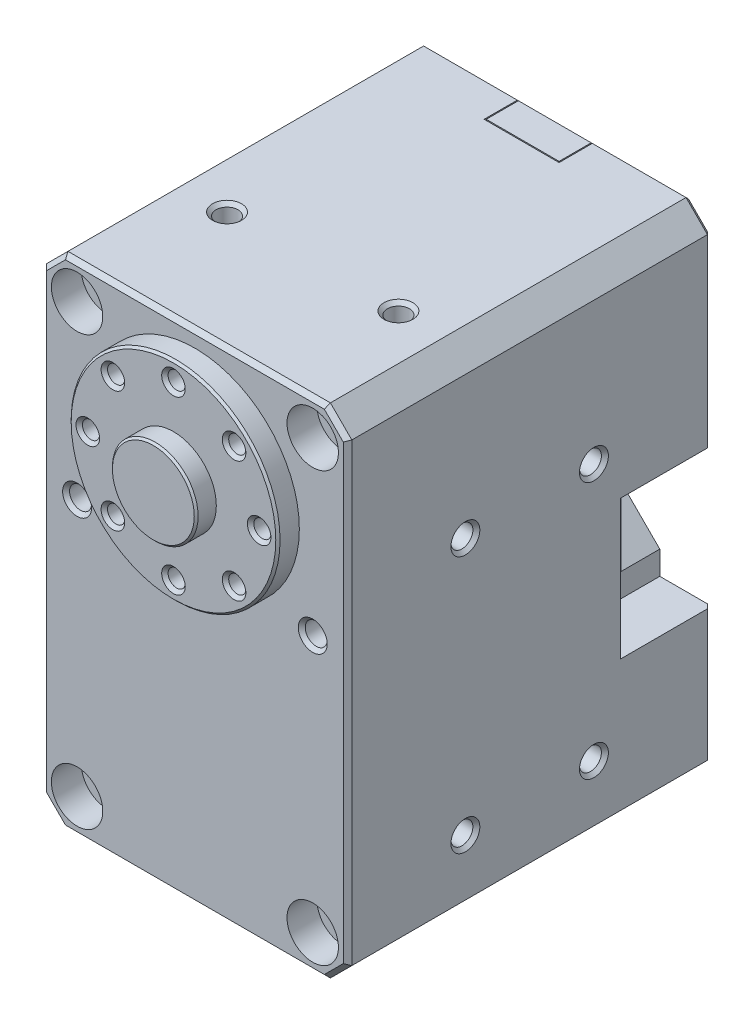
SolidWorks part; units mm, degrees
ref_plane "Front Plane" through (0, 0, 0) normal (0, 0, 1) x (1, 0, 0)
ref_plane "Top Plane" through (0, 0, 0) normal (0, 1, 0) x (1, 0, 0)
ref_plane "Right Plane" through (0, 0, 0) normal (1, 0, 0) x (0, 0, -1)
ref_plane "Plane1" through (0, 0, -17) normal (0, 0, -1) x (-1, 0, 0)
sketch "Sketch1" plane through (0, 0, -17) normal (0, 0, -1) x (-1, 0, 0)
  line L0 (5.5734, -8) -> (-5.5734, -8)
  arc A0 (-5.5734, -8) -> (5.5734, -8) centre (0, 0) ccw
extrude "Boss-Extrude1" add sketch "Sketch1" against normal blind 1
sketch "Sketch2" plane through (0, -8, 0) normal (0, 1, 0) x (-1, 0, 0)
  line L0 (14.25, -16) -> (14.25, -17)
  line L1 (14.25, -17) -> (-5.65, -17)
  line L2 (-5.65, -17) -> (-5.65, -16)
  line L3 (-5.65, -16) -> (14.25, -16)
extrude "Boss-Extrude2" add sketch "Sketch2" along normal blind 19.25
sketch "Sketch3" plane through (0, 0, -16) normal (0, 0, 1) x (1, 0, 0)
  line L0 (5.65, -8) -> (5.5734, -8)
  line L1 (-5.5734, -8) -> (-14.25, -8)
  line L2 (-14.25, -8) -> (-14.25, 11.25)
  line L3 (-14.25, 11.25) -> (5.65, 11.25)
  line L4 (5.65, 11.25) -> (5.65, -8)
  arc A0 (5.5734, -8) -> (-5.5734, -8) centre (0, 0) cw
extrude "Boss-Extrude3" add sketch "Sketch3" along normal blind 2.2
sketch "Sketch4" plane through (0, 0, -13.8) normal (0, 0, 1) x (1, 0, 0)
  line L0 (5.65, -35.25) -> (-14.25, -35.25)
  line L1 (-14.25, -35.25) -> (-14.25, 11.25)
  line L2 (-14.25, 11.25) -> (5.65, 11.25)
  line L3 (5.65, 11.25) -> (5.65, -35.25)
extrude "Boss-Extrude4" add sketch "Sketch4" along normal blind 30.8
sketch "Sketch5" plane through (0, 0, -17) normal (0, 0, -1) x (-1, 0, 0)
  line L0 (5.65, -8) -> (5.65, -7.9461)
  line L1 (5.5734, -8) -> (5.65, -8)
  arc A0 (5.65, -7.9461) -> (5.5734, -8) centre (0, 0) cw
extrude "Cut-Extrude1" cut sketch "Sketch5" against normal blind 1
ref_plane "Plane2" through (0, 0, -13.8) normal (0, 0, 1) x (1, 0, 0)
sketch "Sketch6" plane through (0, 0, -13.8) normal (0, 0, 1) x (1, 0, 0)
  line L0 (5.5734, -8) -> (-5.5734, -8)
  arc A0 (-5.5734, -8) -> (5.5734, -8) centre (0, 0) ccw
extrude "Cut-Extrude2" cut sketch "Sketch6" against normal blind 1.2
sketch "Sketch7" plane through (0, 0, -17) normal (0, 0, -1) x (-1, 0, 0)
  line L0 (-5.65, -8) -> (-5.5734, -8)
  line L1 (-5.65, -7.9461) -> (-5.65, -8)
  arc A0 (-5.5734, -8) -> (-5.65, -7.9461) centre (0, 0) cw
extrude "Cut-Extrude3" cut sketch "Sketch7" against normal blind 1
sketch "Sketch8" plane through (5.65, 0, 0) normal (1, 0, 0) x (0, 0, -1)
  line L0 (13.8, -35.25) -> (-17, -35.25)
  line L1 (-17, -35.25) -> (-17, 11.25)
  line L2 (-17, 11.25) -> (17, 11.25)
  line L3 (17, 11.25) -> (17, -8)
  line L4 (17, -8) -> (13.8, -8)
  line L5 (13.8, -8) -> (13.8, -35.25)
extrude "Boss-Extrude5" add sketch "Sketch8" along normal blind 8.6
sketch "Sketch9" plane through (0, 0, -13.8) normal (0, 0, -1) x (-1, 0, 0)
  line L0 (14.25, -15.5) -> (14.25, -35.25)
  line L1 (14.25, -35.25) -> (-14.25, -35.25)
  line L2 (-14.25, -35.25) -> (-14.25, -15.5)
  line L3 (-14.25, -15.5) -> (14.25, -15.5)
extrude "Boss-Extrude6" add sketch "Sketch9" along normal blind 3.2
sketch "Sketch10" plane through (0, 0, -17) normal (0, 0, -1) x (-1, 0, 0)
  line L0 (-3.5, 11.25) -> (-3.5, 9.45)
  line L1 (-3.5, 9.45) -> (3.5, 9.45)
  line L2 (3.5, 9.45) -> (3.5, 11.25)
  line L3 (3.5, 11.25) -> (-3.5, 11.25)
extrude "Cut-Extrude4" cut sketch "Sketch10" against normal blind 3.5
sketch "Sketch11" plane through (0, 0, -17) normal (0, 0, -1) x (-1, 0, 0)
  line L0 (-2.4, 9.45) -> (2.4, 9.45)
  arc A0 (2.4, 9.45) -> (-2.4, 9.45) centre (0, 0) ccw
extrude "Boss-Extrude7" add sketch "Sketch11" against normal blind 2
sketch "Sketch12" plane through (0, 0, -17) normal (0, 0, -1) x (-1, 0, 0)
  circle A0 centre (0, 0) radius 9.75
extrude "Boss-Extrude8" add sketch "Sketch12" along normal blind 2
ref_plane "Plane3" through (0, 0, -15) normal (0, 0, 1) x (1, 0, 0)
sketch "Sketch13" plane through (0, 0, -15) normal (0, 0, 1) x (1, 0, 0)
  line L0 (1.9647, 9.55) -> (3.4, 9.55)
  line L1 (3.4, 9.55) -> (3.4, 11.25)
  line L2 (3.4, 11.25) -> (-3.4, 11.25)
  line L3 (-3.4, 11.25) -> (-3.4, 9.55)
  line L4 (-3.4, 9.55) -> (-1.9647, 9.55)
  arc A0 (-1.9647, 9.55) -> (1.9647, 9.55) centre (0, 0) cw
extrude "Boss-Extrude9" add sketch "Sketch13" against normal blind 2
sketch "Sketch14" plane through (0, 0, -17) normal (0, 0, -1) x (-1, 0, 0)
  line L0 (9.4, -21) -> (14.25, -21)
  line L1 (14.25, -21) -> (14.25, -15.5)
  line L2 (14.25, -15.5) -> (9.4, -15.5)
  line L3 (9.4, -15.5) -> (9.4, -21)
extrude "Cut-Extrude5" cut sketch "Sketch14" against normal blind 3.2
ref_plane "Plane4" through (0, 0, -13.8) normal (0, 0, -1) x (-1, 0, 0)
ref_plane "Plane5" through (0, 0, -8.5) normal (0, 0, 1) x (1, 0, 0)
sketch "Sketch16" plane through (0, 0, -8.5) normal (0, 0, 1) x (1, 0, 0)
  line L0 (-14.25, -21) -> (-9.4, -21)
  line L1 (-9.4, -21) -> (-9.4, -8)
  line L2 (-9.4, -8) -> (-14.25, -8)
  line L3 (-14.25, -8) -> (-14.25, -21)
extrude "Cut-Extrude6" cut sketch "Sketch16" against normal up to surface up to plane "Plane4"
sketch "Sketch17" plane through (0, 0, -17) normal (0, 0, -1) x (-1, 0, 0)
  line L0 (-9.4, -21) -> (-9.4, -15.5)
  line L1 (-9.4, -15.5) -> (-14.25, -15.5)
  line L2 (-14.25, -15.5) -> (-14.25, -21)
  line L3 (-14.25, -21) -> (-9.4, -21)
extrude "Cut-Extrude7" cut sketch "Sketch17" against normal blind 3.2
sketch "Sketch19" plane through (0, 0, -8.5) normal (0, 0, 1) x (1, 0, 0)
  line L0 (14.25, -8) -> (9.4, -8)
  line L1 (9.4, -8) -> (9.4, -21)
  line L2 (9.4, -21) -> (14.25, -21)
  line L3 (14.25, -21) -> (14.25, -8)
extrude "Cut-Extrude8" cut sketch "Sketch19" against normal up to surface up to plane "Plane4"
ref_plane "Plane6" through (0, 8, 0) normal (0, 1, 0) x (1, 0, 0)
sketch "Sketch20" plane through (0, 8, 0) normal (0, 1, 0) x (1, 0, 0)
  line L0 (-9.65, 8) -> (-11, 8)
  line L1 (-11, 8) -> (-11, 0.8841)
  line L2 (-11, 0.8841) -> (-9.975, 1.5)
  line L3 (-9.975, 1.5) -> (-9.975, 7.675)
  line L4 (-9.975, 7.675) -> (-9.65, 8)
  line L5 (-11, 8) -> (-11, 0.884) construction
revolve "Cut-Revolve1" cut sketch "Sketch20" angle 360 about L5 reverse direction yes
ref_plane "Plane7" through (0, -32, 0) normal (0, 1, 0) x (1, 0, 0)
sketch "Sketch21" plane through (0, -32, 0) normal (0, 1, 0) x (1, 0, 0)
  line L0 (12.35, 8) -> (11, 8)
  line L1 (11, 8) -> (11, 0.8841)
  line L2 (11, 0.8841) -> (12.025, 1.5)
  line L3 (12.025, 1.5) -> (12.025, 7.675)
  line L4 (12.025, 7.675) -> (12.35, 8)
  line L5 (11, 8) -> (11, 0.884) construction
revolve "Cut-Revolve2" cut sketch "Sketch21" angle 360 about L5 reverse direction yes
sketch "Sketch22" plane through (0, -32, 0) normal (0, 1, 0) x (1, 0, 0)
  line L0 (-9.65, 8) -> (-11, 8)
  line L1 (-11, 8) -> (-11, 0.8841)
  line L2 (-11, 0.8841) -> (-9.975, 1.5)
  line L3 (-9.975, 1.5) -> (-9.975, 7.675)
  line L4 (-9.975, 7.675) -> (-9.65, 8)
  line L5 (-11, 8) -> (-11, 0.884) construction
revolve "Cut-Revolve3" cut sketch "Sketch22" angle 360 about L5 reverse direction yes
chamfer "Chamfer1" distance 2 angle 45 4 edges at (-14.25, -35.25, 0) (14.25, -35.25, 0) (-14.25, 11.25, 0) (14.25, 11.25, 0)
chamfer "Chamfer2" distance 3.3 angle 45 2 edges at (-9.4, -15.5, -15.4) (9.4, -15.5, -15.4)
chamfer "Chamfer3" distance 0.4 angle 45 22 edges at (13.25, -34.25, 17) (14.25, -12, 17) (0, -35.25, 17) (13.25, 10.25, 17) (-13.25, -34.25, 17) (0, 11.25, 17) (-14.25, -12, 17) (-13.25, 10.25, 17) (14.25, -27.125, -17) (13.25, -34.25, -17) (0, -35.25, -17) (-14.25, -27.125, -17) (-13.25, -34.25, -17) (-7.875, 11.25, -17) (-14.25, 0.625, -17) (-13.25, 10.25, -17) (0, 11.25, -17) (-9.4, -13.4, -13.8) (7.875, 11.25, -17) (14.25, 0.625, -17) (13.25, 10.25, -17) (9.4, -13.4, -13.8)
chamfer "Chamfer4" distance 0.2 angle 45 1 edges at (-9.75, 0, -19)
sketch "Sketch29" plane through (0, 0, -15) normal (0, 0, 1) x (1, 0, 0)
  line L0 (-3.4, 9.55) -> (-3.4, 11.25)
  line L1 (-3.4, 11.25) -> (3.4, 11.25)
  line L2 (3.4, 11.25) -> (3.4, 9.55)
  line L3 (3.4, 9.55) -> (-3.4, 9.55)
extrude "Boss-Extrude10" add sketch "Sketch29" along normal blind 1.4
hole_wizard "CBORE for M4 Hex Head Machine Screw1" positions "Sketch31" profile "Sketch30" counterbore size "M4" standard "ANSI Metric"
sketch "Sketch31" plane through (0, 0, -8) normal (0, 0, 1) x (1, 0, 0)
  point P0 (-11, -32)
sketch "Sketch30" plane through (-11, -32, -8) normal (1, 0, 0) x (0, -1, 0)
  line L0 (0, 0) -> (0, 9)
  line L1 (0, 9) -> (2.4, 9)
  line L2 (2.4, 9) -> (2.4, 6.2)
  line L3 (2.4, 6.2) -> (1.3, 6.2)
  line L4 (1.3, 6.2) -> (1.3, 0)
  line L5 (1.3, 0) -> (0, 0)
  line L10 (0, 9) -> (-2.4, 9) construction
  line L11 (0, -6.35) -> (0, 107.95) construction
  dimension "Hole Dia." = 4.8
  dimension "Hole Depth" = 9
  dimension "C'Bore Dia." = 2.6
  dimension "C'Bore Depth" = 6.2
  dimension "Drill Angle" = 180
hole_wizard "CBORE for M4 Hex Head Machine Screw2" positions "Sketch33" profile "Sketch32" counterbore size "M4" standard "ANSI Metric"
sketch "Sketch33" plane through (0, 0, -8) normal (0, 0, 1) x (1, 0, 0)
  point P0 (11, -32)
sketch "Sketch32" plane through (11, -32, -8) normal (1, 0, 0) x (0, -1, 0)
  line L0 (0, 0) -> (0, 9)
  line L1 (0, 9) -> (2.4, 9)
  line L2 (2.4, 9) -> (2.4, 6.2)
  line L3 (2.4, 6.2) -> (1.3, 6.2)
  line L4 (1.3, 6.2) -> (1.3, 0)
  line L5 (1.3, 0) -> (0, 0)
  line L10 (0, 9) -> (-2.4, 9) construction
  line L11 (0, -6.35) -> (0, 107.95) construction
  dimension "Hole Dia." = 4.8
  dimension "Hole Depth" = 9
  dimension "C'Bore Dia." = 2.6
  dimension "C'Bore Depth" = 6.2
  dimension "Drill Angle" = 180
hole_wizard "CBORE for M4 Hex Head Machine Screw3" positions "Sketch35" profile "Sketch34" counterbore size "M4" standard "ANSI Metric"
sketch "Sketch35" plane through (0, 0, -8) normal (0, 0, 1) x (1, 0, 0)
  point P0 (-11, 8)
sketch "Sketch34" plane through (-11, 8, -8) normal (1, 0, 0) x (0, -1, 0)
  line L0 (0, 0) -> (0, 9)
  line L1 (0, 9) -> (2.4, 9)
  line L2 (2.4, 9) -> (2.4, 6.2)
  line L3 (2.4, 6.2) -> (1.3, 6.2)
  line L4 (1.3, 6.2) -> (1.3, 0)
  line L5 (1.3, 0) -> (0, 0)
  line L10 (0, 9) -> (-2.4, 9) construction
  line L11 (0, -6.35) -> (0, 107.95) construction
  dimension "Hole Dia." = 4.8
  dimension "Hole Depth" = 9
  dimension "C'Bore Dia." = 2.6
  dimension "C'Bore Depth" = 6.2
  dimension "Drill Angle" = 180
sketch "Sketch45" plane through (0, 8, 0) normal (0, 1, 0) x (1, 0, 0)
  line L0 (13.4, 17) -> (11, 17)
  line L1 (11, 17) -> (11, 0.8841)
  line L2 (11, 0.8841) -> (12.025, 1.5)
  line L3 (12.025, 1.5) -> (12.025, 7.675)
  line L4 (12.025, 7.675) -> (12.35, 8)
  line L5 (12.35, 8) -> (12.3, 8)
  line L6 (12.3, 8) -> (12.3, 14.2)
  line L7 (12.3, 14.2) -> (13.4, 14.2)
  line L8 (13.4, 14.2) -> (13.4, 17)
  line L9 (11, 17) -> (11, 0.884) construction
revolve "Cut-Revolve4" cut sketch "Sketch45" angle 360 about L1 reverse direction yes
ref_plane "Plane8" through (0, 8, 0) normal (0, -1, 0) x (-1, 0, 0)
sketch "Sketch56" plane through (0, 8, 0) normal (0, -1, 0) x (-1, 0, 0)
  line L0 (8.6, -17) -> (11, -17)
  line L1 (11, -17) -> (11, -0.8841)
  line L2 (11, -0.8841) -> (9.975, -1.5)
  line L3 (9.975, -1.5) -> (9.975, -9.675)
  line L4 (9.975, -9.675) -> (9.65, -10)
  line L5 (9.65, -10) -> (9.7, -10)
  line L6 (9.7, -10) -> (9.7, -14.2)
  line L7 (9.7, -14.2) -> (8.6, -14.2)
  line L8 (8.6, -14.2) -> (8.6, -17)
  line L9 (11, -17) -> (11, -0.884) construction
revolve "Cut-Revolve5" cut sketch "Sketch56" angle 360 about L9 reverse direction yes
ref_plane "Plane9" through (0, -32, 0) normal (0, -1, 0) x (-1, 0, 0)
sketch "Sketch68" plane through (0, -32, 0) normal (0, -1, 0) x (-1, 0, 0)
  line L0 (-13.4, -17) -> (-11, -17)
  line L1 (-11, -17) -> (-11, -0.8841)
  line L2 (-11, -0.8841) -> (-12.025, -1.5)
  line L3 (-12.025, -1.5) -> (-12.025, -9.675)
  line L4 (-12.025, -9.675) -> (-12.35, -10)
  line L5 (-12.35, -10) -> (-12.3, -10)
  line L6 (-12.3, -10) -> (-12.3, -14.2)
  line L7 (-12.3, -14.2) -> (-13.4, -14.2)
  line L8 (-13.4, -14.2) -> (-13.4, -17)
  line L9 (-11, -17) -> (-11, -0.884) construction
revolve "Cut-Revolve6" cut sketch "Sketch68" angle 360 about L9 reverse direction yes
sketch "Sketch81" plane through (0, -32, 0) normal (0, -1, 0) x (-1, 0, 0)
  line L0 (8.6, -17) -> (11, -17)
  line L1 (11, -17) -> (11, -0.8841)
  line L2 (11, -0.8841) -> (9.975, -1.5)
  line L3 (9.975, -1.5) -> (9.975, -9.675)
  line L4 (9.975, -9.675) -> (9.65, -10)
  line L5 (9.65, -10) -> (9.7, -10)
  line L6 (9.7, -10) -> (9.7, -14.2)
  line L7 (9.7, -14.2) -> (8.6, -14.2)
  line L8 (8.6, -14.2) -> (8.6, -17)
  line L9 (11, -17) -> (11, -0.884) construction
revolve "Cut-Revolve7" cut sketch "Sketch81" angle 360 about L9 reverse direction yes
sketch "Sketch93" plane through (0, 8, 0) normal (0, -1, 0) x (-1, 0, 0)
  line L0 (-13.4, -17) -> (-11, -17)
  line L1 (-11, -17) -> (-11, -0.8841)
  line L2 (-11, -0.8841) -> (-12.025, -1.5)
  line L3 (-12.025, -1.5) -> (-12.025, -9.675)
  line L4 (-12.025, -9.675) -> (-12.35, -10)
  line L5 (-12.35, -10) -> (-12.3, -10)
  line L6 (-12.3, -10) -> (-12.3, -14.2)
  line L7 (-12.3, -14.2) -> (-13.4, -14.2)
  line L8 (-13.4, -14.2) -> (-13.4, -17)
  line L9 (-11, -17) -> (-11, -0.884) construction
revolve "Cut-Revolve8" cut sketch "Sketch93" angle 360 about L9 reverse direction yes
sketch "Sketch96" plane through (0, 0, 0) normal (0, 1, 0) x (1, 0, 0)
  line L0 (9.75, -17) -> (0, -17)
  line L1 (0, -17) -> (0, -20.8794)
  line L2 (0, -20.8794) -> (3.8206, -20.8794)
  line L3 (3.8206, -20.8794) -> (4, -20.7)
  line L4 (4, -20.7) -> (4, -19)
  line L5 (4, -19) -> (9.55, -19)
  line L6 (9.55, -19) -> (9.75, -18.8)
  line L7 (9.75, -18.8) -> (9.75, -17)
  line L8 (0, -17) -> (0, -20.8794) construction
revolve "Revolve1" add sketch "Sketch96" angle 360 about L1 reverse direction yes
hole_wizard "Ø1.6 (1.6) Diameter Hole1" positions "Sketch98" profile "Sketch97" hole size "Ø1.6" standard "ANSI Metric"
sketch "Sketch98" plane through (0, 0, -19) normal (0, 0, -1) x (-1, 0, 0)
  point P0 (5.6569, 5.6569)
  point P1 (8, 0)
  point P2 (5.6569, -5.6569)
  point P3 (0, -8)
  point P4 (-5.6569, -5.6569)
  point P5 (-8, 0)
  point P6 (-5.6569, 5.6569)
  point P7 (0, 8)
sketch "Sketch97" plane through (-5.6569, 5.6569, -19) normal (1, 0, 0) x (0, 1, 0)
  line L0 (0, 0) -> (0, 2)
  line L1 (0, 2) -> (0.8, 2)
  line L2 (0.8, 2) -> (0.8, 0.3)
  line L3 (0.8, 0.3) -> (1.1, 0)
  line L5 (1.1, 0) -> (0, 0)
  line L6 (-0.8, 0.3) -> (-1.1, 0) construction
  line L10 (0, 2) -> (-0.8, 2) construction
  line L11 (0, -6.35) -> (0, 107.95) construction
  dimension "Hole Dia." = 1.6
  dimension "Hole Depth" = 2
  dimension "Near C'Sink Dia." = 2.2
  dimension "Near C'Sink Angle" = 90
  dimension "Drill Angle" = 180
hole_wizard "CSK for M8 Flat Head Machine Screw1" positions "Sketch100" profile "Sketch99" countersink size "M8" standard "ANSI Metric"
sketch "Sketch100" plane through (0, 0, -19) normal (0, 0, -1) x (-1, 0, 0)
  point P0 (0, 0)
sketch "Sketch99" plane through (0, 0, -19) normal (1, 0, 0) x (0, 1, 0)
  line L0 (0, 0) -> (0, 2)
  line L1 (0, 2) -> (4.75, 2)
  line L2 (4.75, 2) -> (4.75, 0.8)
  line L3 (4.75, 0.8) -> (5.05, 0.5)
  line L4 (5.05, 0.5) -> (5.05, 0)
  line L6 (5.05, 0) -> (0, 0)
  line L7 (-4.75, 0.8) -> (-5.05, 0.5) construction
  line L10 (0, 2) -> (-4.75, 2) construction
  line L11 (0, -6.35) -> (0, 107.95) construction
  dimension "Hole Dia." = 9.5
  dimension "Hole Depth" = 2
  dimension "C'Sink Dia." = 10.1
  dimension "C'Sink Angle" = 90
  dimension "Drill Angle" = 180
  dimension "Head Clearance" = 0.5
hole_wizard "Ø1.6 (1.6) Diameter Hole2" positions "Sketch102" profile "Sketch101" hole size "Ø1.6" standard "ANSI Metric"
sketch "Sketch102" plane through (0, 0, 19) normal (0, 0, 1) x (1, 0, 0)
  point P0 (5.6569, 5.6569)
  point P1 (8, 0)
  point P2 (5.6569, -5.6569)
  point P3 (0, -8)
  point P4 (-5.6569, -5.6569)
  point P5 (-8, 0)
  point P6 (-5.6569, 5.6569)
  point P7 (0, 8)
sketch "Sketch101" plane through (5.6569, 5.6569, 19) normal (1, 0, 0) x (0, -1, 0)
  line L0 (0, 0) -> (0, 2)
  line L1 (0, 2) -> (0.8, 2)
  line L2 (0.8, 2) -> (0.8, 0.3)
  line L3 (0.8, 0.3) -> (1.1, 0)
  line L5 (1.1, 0) -> (0, 0)
  line L6 (-0.8, 0.3) -> (-1.1, 0) construction
  line L10 (0, 2) -> (-0.8, 2) construction
  line L11 (0, -6.35) -> (0, 107.95) construction
  dimension "Hole Dia." = 1.6
  dimension "Hole Depth" = 2
  dimension "Near C'Sink Dia." = 2.2
  dimension "Near C'Sink Angle" = 90
  dimension "Drill Angle" = 180
hole_wizard "Ø2.05 (2.05) Diameter Hole1" positions "Sketch104" profile "Sketch103" hole size "Ø2.05" standard "ANSI Metric"
sketch "Sketch104" plane through (0, -35.25, 0) normal (0, -1, 0) x (-1, 0, 0)
  point P0 (-8, -6)
  point P1 (8, 6)
  point P2 (-8, 6)
  point P3 (8, -6)
sketch "Sketch103" plane through (8, -35.25, 6) normal (1, 0, 0) x (0, 0, -1)
  line L0 (0, 0) -> (0, 3)
  line L1 (0, 3) -> (1.025, 3)
  line L2 (1.025, 3) -> (1.025, 0.325)
  line L3 (1.025, 0.325) -> (1.35, 0)
  line L5 (1.35, 0) -> (0, 0)
  line L6 (-1.025, 0.325) -> (-1.35, 0) construction
  line L10 (0, 3) -> (-1.025, 3) construction
  line L11 (0, -6.35) -> (0, 107.95) construction
  dimension "Hole Dia." = 2.05
  dimension "Hole Depth" = 3
  dimension "Near C'Sink Dia." = 2.7
  dimension "Near C'Sink Angle" = 90
  dimension "Drill Angle" = 180
hole_wizard "Ø2.05 (2.05) Diameter Hole2" positions "Sketch106" profile "Sketch105" hole size "Ø2.05" standard "ANSI Metric"
sketch "Sketch106" plane through (-14.25, 0, 0) normal (-1, 0, 0) x (0, 0, 1)
  point P0 (-6, -4)
  point P1 (6, -28)
  point P2 (-6, -28)
  point P3 (6, -4)
sketch "Sketch105" plane through (-14.25, -4, -6) normal (0, 1, 0) x (0, 0, 1)
  line L0 (0, 0) -> (0, 3)
  line L1 (0, 3) -> (1.025, 3)
  line L2 (1.025, 3) -> (1.025, 0.325)
  line L3 (1.025, 0.325) -> (1.35, 0)
  line L5 (1.35, 0) -> (0, 0)
  line L6 (-1.025, 0.325) -> (-1.35, 0) construction
  line L10 (0, 3) -> (-1.025, 3) construction
  line L11 (0, -6.35) -> (0, 107.95) construction
  dimension "Hole Dia." = 2.05
  dimension "Hole Depth" = 3
  dimension "Near C'Sink Dia." = 2.7
  dimension "Near C'Sink Angle" = 90
  dimension "Drill Angle" = 180
hole_wizard "Ø2.05 (2.05) Diameter Hole3" positions "Sketch108" profile "Sketch107" hole size "Ø2.05" standard "ANSI Metric"
sketch "Sketch108" plane through (0, 11.25, 0) normal (0, 1, 0) x (1, 0, 0)
  point P0 (-8, -6)
  point P1 (8, -6)
sketch "Sketch107" plane through (-8, 11.25, 6) normal (1, 0, 0) x (0, 0, 1)
  line L0 (0, 0) -> (0, 3)
  line L1 (0, 3) -> (1.025, 3)
  line L2 (1.025, 3) -> (1.025, 0.325)
  line L3 (1.025, 0.325) -> (1.35, 0)
  line L5 (1.35, 0) -> (0, 0)
  line L6 (-1.025, 0.325) -> (-1.35, 0) construction
  line L10 (0, 3) -> (-1.025, 3) construction
  line L11 (0, -6.35) -> (0, 107.95) construction
  dimension "Hole Dia." = 2.05
  dimension "Hole Depth" = 3
  dimension "Near C'Sink Dia." = 2.7
  dimension "Near C'Sink Angle" = 90
  dimension "Drill Angle" = 180
hole_wizard "Ø2.05 (2.05) Diameter Hole4" positions "Sketch110" profile "Sketch109" hole size "Ø2.05" standard "ANSI Metric"
sketch "Sketch110" plane through (0, 0, 17) normal (0, 0, 1) x (1, 0, 0)
  point P0 (-11, -8)
  point P1 (11, -8)
sketch "Sketch109" plane through (-11, -8, 17) normal (1, 0, 0) x (0, -1, 0)
  line L0 (0, 0) -> (0, 3)
  line L1 (0, 3) -> (1.025, 3)
  line L2 (1.025, 3) -> (1.025, 0.325)
  line L3 (1.025, 0.325) -> (1.35, 0)
  line L5 (1.35, 0) -> (0, 0)
  line L6 (-1.025, 0.325) -> (-1.35, 0) construction
  line L10 (0, 3) -> (-1.025, 3) construction
  line L11 (0, -6.35) -> (0, 107.95) construction
  dimension "Hole Dia." = 2.05
  dimension "Hole Depth" = 3
  dimension "Near C'Sink Dia." = 2.7
  dimension "Near C'Sink Angle" = 90
  dimension "Drill Angle" = 180
hole_wizard "Ø2.05 (2.05) Diameter Hole5" positions "Sketch112" profile "Sketch111" hole size "Ø2.05" standard "ANSI Metric"
sketch "Sketch112" plane through (14.25, 0, 0) normal (1, 0, 0) x (0, 0, -1)
  point P0 (6, -4)
  point P1 (-6, -28)
  point P2 (6, -28)
  point P3 (-6, -4)
sketch "Sketch111" plane through (14.25, -4, -6) normal (0, 1, 0) x (0, 0, -1)
  line L0 (0, 0) -> (0, 3)
  line L1 (0, 3) -> (1.025, 3)
  line L2 (1.025, 3) -> (1.025, 0.325)
  line L3 (1.025, 0.325) -> (1.35, 0)
  line L5 (1.35, 0) -> (0, 0)
  line L6 (-1.025, 0.325) -> (-1.35, 0) construction
  line L10 (0, 3) -> (-1.025, 3) construction
  line L11 (0, -6.35) -> (0, 107.95) construction
  dimension "Hole Dia." = 2.05
  dimension "Hole Depth" = 3
  dimension "Near C'Sink Dia." = 2.7
  dimension "Near C'Sink Angle" = 90
  dimension "Drill Angle" = 180
sketch "Sketch113" plane through (0, 0, -19) normal (0, 0, -1) x (-1, 0, 0)
  circle A0 centre (0, 0) radius 12.5
extrude "Cut-Extrude9" cut sketch "Sketch113" against normal up to surface (2 mm away) up to face at (-8.6, 8, -17)
